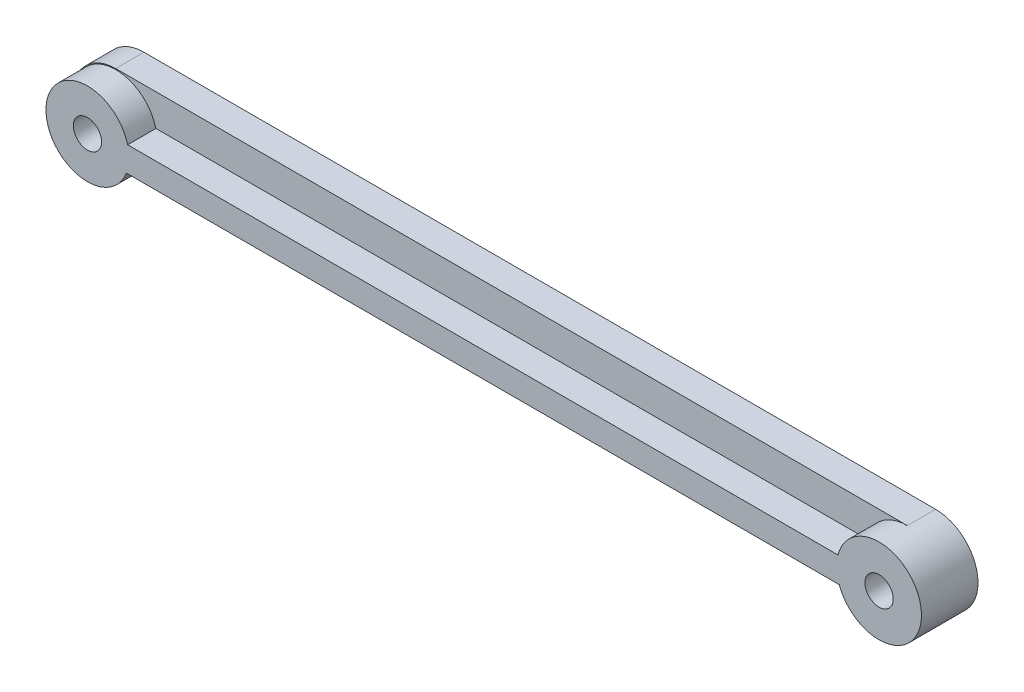
SolidWorks part; units mm, degrees
ref_plane "前视基准面" through (0, 0, 0) normal (0, 0, 1) x (1, 0, 0)
ref_plane "上视基准面" through (0, 0, 0) normal (0, 1, 0) x (1, 0, 0)
ref_plane "右视基准面" through (0, 0, 0) normal (1, 0, 0) x (0, 0, -1)
other "Configuration Table"
sketch "草图1" plane through (0, 0, 0) normal (0, 0, 1) x (1, 0, 0)
  line L0 (-1000, 0) -> (0, 0) construction
  line L2 (0, 1.5) -> (28, 1.5)
  line L3 (0, -1.5) -> (28, -1.5)
  line L4 (29.5, 0) -> (49000, 0) construction
  arc A0 (0, 1.5) -> (0, -1.5) centre (0, 0) ccw
  arc A1 (28, -1.5) -> (28, 1.5) centre (28, 0) ccw
  circle A2 centre (0, 0) radius 0.5
  circle A3 centre (28, 0) radius 0.5
  dimension "D1" = 3
  dimension "D3" = 1.5
  dimension "D4" = 1
  dimension "D5" = 1
  dimension "D2" = 28
extrude "凸台-拉伸1" add sketch "草图1" along normal blind 1
sketch "草图2" plane through (0, 0, 1) normal (0, 0, 1) x (1, 0, 0)
  line L0 (1.4203, 0.3745) -> (26.5475, 0.3745)
  line L1 (26.5907, -0.5138) -> (1.3761, -0.5138)
  arc A0 (1.4203, 0.3745) -> (1.3761, -0.5138) centre (0, 0) ccw
  arc A2 (26.5907, -0.5138) -> (26.5475, 0.3745) centre (28, 0) ccw
  circle A4 centre (0, 0) radius 0.5
  circle A5 centre (28, 0) radius 0.5
  point P8 (26.6015, 0.3768)
extrude "凸台-拉伸3" add sketch "草图2" along normal blind 1
